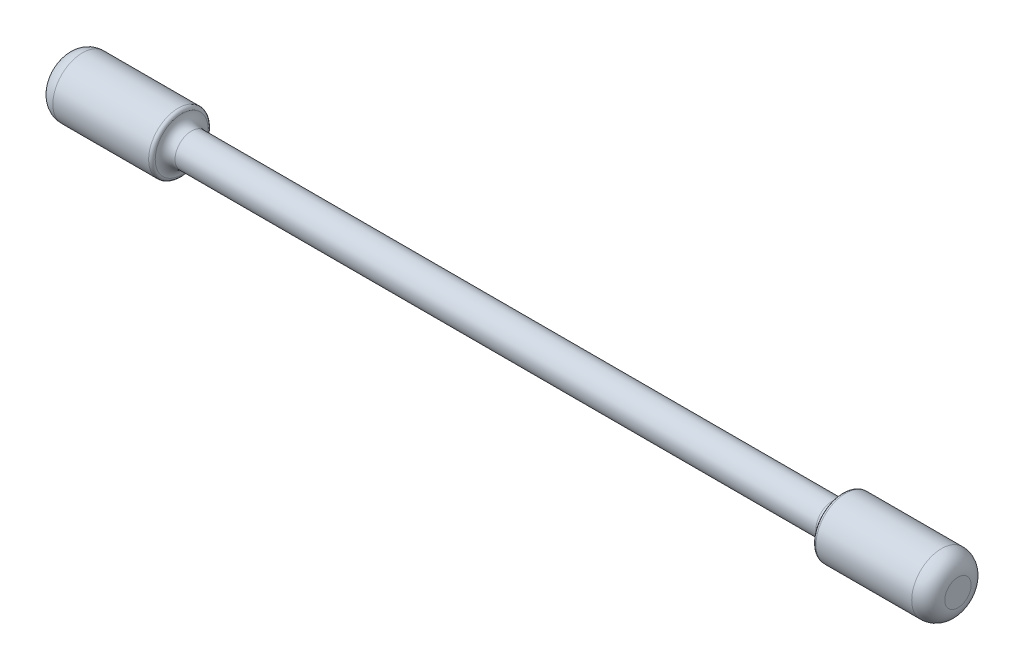
SolidWorks part; units mm, degrees
ref_plane "Front Plane" through (0, 0, 0) normal (0, 0, 1) x (1, 0, 0)
ref_plane "Top Plane" through (0, 0, 0) normal (0, 1, 0) x (1, 0, 0)
ref_plane "Right Plane" through (0, 0, 0) normal (1, 0, 0) x (0, 0, -1)
sketch "Sketch1" plane through (0, 0, 0) normal (0, 1, 0) x (1, 0, 0)
  line L0 (135, 0) -> (-135, 0)
  line L1 (-135, 0) -> (-135, -9)
  line L2 (-135, -9) -> (-100, -9)
  line L3 (-100, -9) -> (-100, -5)
  line L4 (-100, -5) -> (100, -5)
  line L5 (100, -5) -> (100, -9)
  line L6 (100, -9) -> (135, -9)
  line L7 (135, -9) -> (135, 0)
  point P4 (0, 0)
  dimension "D1" = 270
  dimension "D2" = 200
  dimension "D3" = 35
  dimension "D4" = 35
  dimension "D5" = 9
  dimension "D6" = 5
revolve "Revolve1" add sketch "Sketch1" angle 360 about L0
fillet "Fillet1" radius 3 2 edges at (100, 0, -5) (-100, 0, -5)
fillet "Fillet2" radius 1 2 edges at (100, 0, -9) (-100, 0, -9)
fillet "Fillet3" radius 5 2 edges at (-135, 0, -9) (135, 0, -9)
